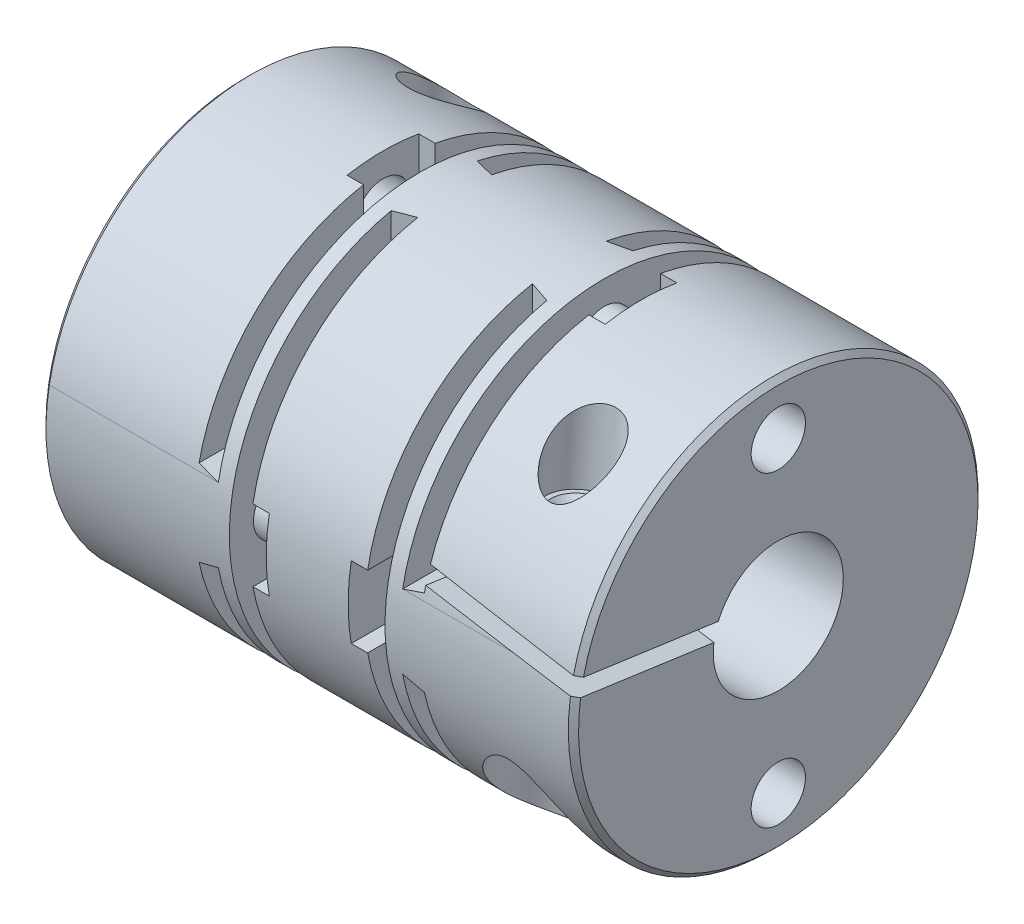
SolidWorks part; units mm, degrees
ref_plane "Front Plane" through (0, 0, 0) normal (0, 0, 1) x (1, 0, 0)
ref_plane "Top Plane" through (0, 0, 0) normal (0, 1, 0) x (1, 0, 0)
ref_plane "Right Plane" through (0, 0, 0) normal (1, 0, 0) x (0, 0, -1)
ref_plane "Plane1" through (0, 0, 0) normal (0, 0, 1) x (1, 0, 0)
sketch "Sketch1" plane through (0, 0, 0) normal (0, 0, 1) x (1, 0, 0)
  line L0 (0, 3.175) -> (7.5, 3.175)
  line L1 (7.5, 3.175) -> (7.5, 4.05)
  line L2 (7.5, 4.05) -> (18.5, 4.05)
  line L3 (18.5, 4.05) -> (18.5, 3.175)
  line L4 (18.5, 3.175) -> (26, 3.175)
  line L5 (26, 3.175) -> (26, 9.75)
  line L6 (26, 9.75) -> (25.75, 10)
  line L7 (25.75, 10) -> (0.25, 10)
  line L8 (0.25, 10) -> (0, 9.75)
  line L9 (0, 9.75) -> (0, 3.175)
  line L10 (26, 0) -> (0, 0) construction
revolve "Revolve1" add sketch "Sketch1" angle 360 about L10 reverse direction yes
ref_plane "Plane2" through (0, 0, 0) normal (0, -0.1392, 0.9903) x (1, 0, 0)
sketch "Sketch2" plane through (0, 0, 0) normal (0, -0.1392, 0.9903) x (1, 0, 0)
  line L0 (-1.3514, 1.4356) -> (-1.24, 0.6434)
  line L1 (-1.24, 0.6434) -> (8.5, 2.0122)
  line L2 (8.5, 2.0122) -> (8.5, 2.8201)
  line L3 (8.5, 2.8201) -> (-1.3514, 1.4356)
extrude "Cut-Extrude1" cut sketch "Sketch2" against normal blind 10
ref_plane "Plane3" through (0, 0, 0) normal (0, 0.1392, 0.9903) x (1, 0, 0)
sketch "Sketch3" plane through (0, 0, 0) normal (0, 0.1392, 0.9903) x (1, 0, 0)
  line L0 (17.5, 1.1492) -> (26, 0)
  line L1 (26, 0) -> (26.1072, 0.7928)
  line L2 (26.1072, 0.7928) -> (17.5, 1.9565)
  line L3 (17.5, 1.9565) -> (17.5, 1.1492)
extrude "Cut-Extrude2" cut sketch "Sketch3" along normal blind 10
ref_plane "Plane4" through (3.7, 0, 0) normal (1, 0, 0) x (0, 0, -1)
sketch "Sketch4" plane through (3.7, 0, 0) normal (1, 0, 0) x (0, 0, -1)
  line L0 (5.6037, 10.5285) -> (7.098, 10.6592)
  line L1 (7.098, 10.6592) -> (7.5338, 5.6782)
  line L2 (7.5338, 5.6782) -> (7.2847, 5.6564)
  line L3 (7.2847, 5.6564) -> (7.0634, 5.3926)
  line L4 (7.0634, 5.3926) -> (7.4567, 0.8968)
  line L5 (7.4567, 0.8968) -> (7.7205, 0.6755)
  line L6 (7.7205, 0.6755) -> (7.982, -2.3131)
  line L7 (7.982, -2.3131) -> (9.4016, -2.1889)
  line L8 (9.4016, -2.1889) -> (10.0116, -9.1623)
  line L9 (10.0116, -9.1623) -> (7.3468, -9.3954)
  line L10 (7.3468, -9.3954) -> (5.6037, 10.5285)
  line L11 (7.3468, -9.3954) -> (5.6037, 10.5285) construction
revolve "Cut-Revolve1" cut sketch "Sketch4" angle 360 about L11 reverse direction yes
ref_plane "Plane5" through (22.3, 0, 0) normal (1, 0, 0) x (0, 0, -1)
sketch "Sketch5" plane through (22.3, 0, 0) normal (1, 0, 0) x (0, 0, -1)
  line L0 (-5.6037, 10.5285) -> (-4.1094, 10.3977)
  line L1 (-4.1094, 10.3977) -> (-4.5452, 5.4168)
  line L2 (-4.5452, 5.4168) -> (-4.7942, 5.4385)
  line L3 (-4.7942, 5.4385) -> (-5.058, 5.2172)
  line L4 (-5.058, 5.2172) -> (-5.3816, 1.5183)
  line L5 (-5.3816, 1.5183) -> (-5.1603, 1.2545)
  line L6 (-5.1603, 1.2545) -> (-5.4915, -2.531)
  line L7 (-5.4915, -2.531) -> (-4.0719, -2.6552)
  line L8 (-4.0719, -2.6552) -> (-4.682, -9.6286)
  line L9 (-4.682, -9.6286) -> (-7.3468, -9.3954)
  line L10 (-7.3468, -9.3954) -> (-5.6037, 10.5285)
  line L11 (-7.3468, -9.3954) -> (-5.6037, 10.5285) construction
revolve "Cut-Revolve2" cut sketch "Sketch5" angle 360 about L11 reverse direction yes
ref_plane "Plane6" through (0, 0, 0) normal (0, 0, 1) x (1, 0, 0)
sketch "Sketch6" plane through (0, 0, 0) normal (0, 0, 1) x (1, 0, 0)
  line L0 (7.5, 10.5) -> (7.5, 2.1)
  line L1 (7.5, 2.1) -> (8.5, 1.8)
  line L2 (8.5, 1.8) -> (8.5, 10)
  line L3 (8.5, 10) -> (17.5, 10)
  line L4 (17.5, 10) -> (17.5, 1.8)
  line L5 (17.5, 1.8) -> (18.5, 2.1)
  line L6 (18.5, 2.1) -> (18.5, 10.5)
  line L7 (18.5, 10.5) -> (7.5, 10.5)
extrude "Cut-Extrude3" cut sketch "Sketch6" against normal blind 10 and the other way blind 10
ref_plane "Plane7" through (0, 0, 0) normal (0, 0, 1) x (1, 0, 0)
sketch "Sketch7" plane through (0, 0, 0) normal (0, 0, 1) x (1, 0, 0)
  line L0 (7.5, -10.5) -> (18.5, -10.5)
  line L1 (18.5, -10.5) -> (18.5, -2.1)
  line L2 (18.5, -2.1) -> (17.5, -1.8)
  line L3 (17.5, -1.8) -> (17.5, -10)
  line L4 (17.5, -10) -> (8.5, -10)
  line L5 (8.5, -10) -> (8.5, -1.8)
  line L6 (8.5, -1.8) -> (7.5, -2.1)
  line L7 (7.5, -2.1) -> (7.5, -10.5)
extrude "Cut-Extrude4" cut sketch "Sketch7" against normal blind 10 and the other way blind 10
ref_plane "Plane8" through (0, 0, 0) normal (0, 1, 0) x (-1, 0, 0)
sketch "Sketch8" plane through (0, 0, 0) normal (0, 1, 0) x (-1, 0, 0)
  line L0 (-9.2, -10.5) -> (-9.2, -2.1)
  line L1 (-9.2, -2.1) -> (-10.2, -1.8)
  line L2 (-10.2, -1.8) -> (-10.2, -10)
  line L3 (-10.2, -10) -> (-15.8, -10)
  line L4 (-15.8, -10) -> (-15.8, -1.8)
  line L5 (-15.8, -1.8) -> (-16.8, -2.1)
  line L6 (-16.8, -2.1) -> (-16.8, -10.5)
  line L7 (-16.8, -10.5) -> (-9.2, -10.5)
extrude "Cut-Extrude5" cut sketch "Sketch8" against normal blind 10 and the other way blind 10
ref_plane "Plane9" through (0, 0, 0) normal (0, 1, 0) x (-1, 0, 0)
sketch "Sketch9" plane through (0, 0, 0) normal (0, 1, 0) x (-1, 0, 0)
  line L0 (-9.2, 10.5) -> (-16.8, 10.5)
  line L1 (-16.8, 10.5) -> (-16.8, 2.1)
  line L2 (-16.8, 2.1) -> (-15.8, 1.8)
  line L3 (-15.8, 1.8) -> (-15.8, 10)
  line L4 (-15.8, 10) -> (-10.2, 10)
  line L5 (-10.2, 10) -> (-10.2, 1.8)
  line L6 (-10.2, 1.8) -> (-9.2, 2.1)
  line L7 (-9.2, 2.1) -> (-9.2, 10.5)
extrude "Cut-Extrude6" cut sketch "Sketch9" against normal blind 10 and the other way blind 10
ref_plane "Plane10" through (15.8, 0, 0) normal (1, 0, 0) x (0, 0, -1)
sketch "Sketch10" plane through (15.8, 0, 0) normal (1, 0, 0) x (0, 0, -1)
  line L0 (-10, -1.75) -> (-7.5, -1.75)
  line L1 (-7.5, 1.75) -> (-10, 1.75)
  line L2 (-10, 1.75) -> (-10, -1.75)
  arc A0 (-7.5, -1.75) -> (-7.5, 1.75) centre (-7.5, 0) ccw
extrude "Cut-Extrude7" cut sketch "Sketch10" against normal blind 0.8
ref_plane "Plane11" through (15.8, 0, 0) normal (1, 0, 0) x (0, 0, -1)
sketch "Sketch11" plane through (15.8, 0, 0) normal (1, 0, 0) x (0, 0, -1)
  line L0 (7.5, -1.75) -> (10, -1.75)
  line L1 (10, -1.75) -> (10, 1.75)
  line L2 (10, 1.75) -> (7.5, 1.75)
  arc A0 (7.5, 1.75) -> (7.5, -1.75) centre (7.5, 0) ccw
extrude "Cut-Extrude8" cut sketch "Sketch11" against normal blind 0.8
ref_plane "Plane12" through (10.2, 0, 0) normal (1, 0, 0) x (0, 0, -1)
sketch "Sketch12" plane through (10.2, 0, 0) normal (1, 0, 0) x (0, 0, -1)
  line L0 (-10, -1.75) -> (-7.5, -1.75)
  line L1 (-7.5, 1.75) -> (-10, 1.75)
  line L2 (-10, 1.75) -> (-10, -1.75)
  arc A0 (-7.5, -1.75) -> (-7.5, 1.75) centre (-7.5, 0) ccw
extrude "Cut-Extrude9" cut sketch "Sketch12" along normal blind 0.8
ref_plane "Plane13" through (10.2, 0, 0) normal (1, 0, 0) x (0, 0, -1)
sketch "Sketch13" plane through (10.2, 0, 0) normal (1, 0, 0) x (0, 0, -1)
  line L0 (7.5, -1.75) -> (10, -1.75)
  line L1 (10, -1.75) -> (10, 1.75)
  line L2 (10, 1.75) -> (7.5, 1.75)
  arc A0 (7.5, 1.75) -> (7.5, -1.75) centre (7.5, 0) ccw
extrude "Cut-Extrude10" cut sketch "Sketch13" along normal blind 0.8
ref_plane "Plane14" through (7.5, 0, 0) normal (1, 0, 0) x (0, 0, -1)
sketch "Sketch14" plane through (7.5, 0, 0) normal (1, 0, 0) x (0, 0, -1)
  line L0 (1.75, 7.5) -> (1.75, 10)
  line L1 (1.75, 10) -> (-1.75, 10)
  line L2 (-1.75, 10) -> (-1.75, 7.5)
  arc A0 (-1.75, 7.5) -> (1.75, 7.5) centre (0, 7.5) ccw
extrude "Cut-Extrude11" cut sketch "Sketch14" against normal blind 0.8
ref_plane "Plane15" through (7.5, 0, 0) normal (1, 0, 0) x (0, 0, -1)
sketch "Sketch15" plane through (7.5, 0, 0) normal (1, 0, 0) x (0, 0, -1)
  line L0 (-1.75, -7.5) -> (-1.75, -10)
  line L1 (-1.75, -10) -> (1.75, -10)
  line L2 (1.75, -10) -> (1.75, -7.5)
  arc A0 (1.75, -7.5) -> (-1.75, -7.5) centre (0, -7.5) ccw
extrude "Cut-Extrude12" cut sketch "Sketch15" against normal blind 0.8
ref_plane "Plane16" through (18.5, 0, 0) normal (1, 0, 0) x (0, 0, -1)
sketch "Sketch16" plane through (18.5, 0, 0) normal (1, 0, 0) x (0, 0, -1)
  line L0 (1.75, 7.5) -> (1.75, 10)
  line L1 (1.75, 10) -> (-1.75, 10)
  line L2 (-1.75, 10) -> (-1.75, 7.5)
  arc A0 (-1.75, 7.5) -> (1.75, 7.5) centre (0, 7.5) ccw
extrude "Cut-Extrude13" cut sketch "Sketch16" along normal blind 0.8
ref_plane "Plane17" through (18.5, 0, 0) normal (1, 0, 0) x (0, 0, -1)
sketch "Sketch17" plane through (18.5, 0, 0) normal (1, 0, 0) x (0, 0, -1)
  line L0 (-1.75, -7.5) -> (-1.75, -10)
  line L1 (-1.75, -10) -> (1.75, -10)
  line L2 (1.75, -10) -> (1.75, -7.5)
  arc A0 (1.75, -7.5) -> (-1.75, -7.5) centre (0, -7.5) ccw
extrude "Cut-Extrude14" cut sketch "Sketch17" along normal blind 0.8
ref_plane "Plane18" through (9.2, 0, 0) normal (1, 0, 0) x (0, 0, -1)
sketch "Sketch18" plane through (9.2, 0, 0) normal (1, 0, 0) x (0, 0, -1)
  circle A0 centre (-7.5, 0) radius 1.325
extrude "Boss-Extrude1" add sketch "Sketch18" along normal blind 0.8
ref_plane "Plane19" through (9.2, 0, 0) normal (1, 0, 0) x (0, 0, -1)
sketch "Sketch19" plane through (9.2, 0, 0) normal (1, 0, 0) x (0, 0, -1)
  circle A0 centre (7.5, 0) radius 1.325
extrude "Boss-Extrude2" add sketch "Sketch19" along normal blind 0.8
ref_plane "Plane20" through (8.5, 0, 0) normal (1, 0, 0) x (0, 0, -1)
sketch "Sketch20" plane through (8.5, 0, 0) normal (1, 0, 0) x (0, 0, -1)
  circle A0 centre (0, 7.5) radius 1.325
extrude "Boss-Extrude3" add sketch "Sketch20" against normal blind 0.8
ref_plane "Plane21" through (8.5, 0, 0) normal (1, 0, 0) x (0, 0, -1)
sketch "Sketch21" plane through (8.5, 0, 0) normal (1, 0, 0) x (0, 0, -1)
  circle A0 centre (0, -7.5) radius 1.325
extrude "Boss-Extrude4" add sketch "Sketch21" against normal blind 0.8
ref_plane "Plane22" through (16.8, 0, 0) normal (1, 0, 0) x (0, 0, -1)
sketch "Sketch22" plane through (16.8, 0, 0) normal (1, 0, 0) x (0, 0, -1)
  circle A0 centre (-7.5, 0) radius 1.325
extrude "Boss-Extrude5" add sketch "Sketch22" against normal blind 0.8
ref_plane "Plane23" through (16.8, 0, 0) normal (1, 0, 0) x (0, 0, -1)
sketch "Sketch23" plane through (16.8, 0, 0) normal (1, 0, 0) x (0, 0, -1)
  circle A0 centre (7.5, 0) radius 1.325
extrude "Boss-Extrude6" add sketch "Sketch23" against normal blind 0.8
ref_plane "Plane24" through (17.5, 0, 0) normal (1, 0, 0) x (0, 0, -1)
sketch "Sketch24" plane through (17.5, 0, 0) normal (1, 0, 0) x (0, 0, -1)
  circle A0 centre (0, 7.5) radius 1.325
extrude "Boss-Extrude7" add sketch "Sketch24" along normal blind 0.8
ref_plane "Plane25" through (17.5, 0, 0) normal (1, 0, 0) x (0, 0, -1)
sketch "Sketch25" plane through (17.5, 0, 0) normal (1, 0, 0) x (0, 0, -1)
  circle A0 centre (0, -7.5) radius 1.325
extrude "Boss-Extrude8" add sketch "Sketch25" along normal blind 0.8
ref_plane "Plane26" through (0, 0, 0) normal (1, 0, 0) x (0, 0, -1)
sketch "Sketch26" plane through (0, 0, 0) normal (1, 0, 0) x (0, 0, -1)
  circle A0 centre (0, 7.5) radius 1.325
extrude "Cut-Extrude15" cut sketch "Sketch26" along normal blind 7.5
ref_plane "Plane27" through (0, 0, 0) normal (1, 0, 0) x (0, 0, -1)
sketch "Sketch27" plane through (0, 0, 0) normal (1, 0, 0) x (0, 0, -1)
  circle A0 centre (0, -7.5) radius 1.325
extrude "Cut-Extrude16" cut sketch "Sketch27" along normal blind 7.5
ref_plane "Plane28" through (26, 0, 0) normal (1, 0, 0) x (0, 0, -1)
sketch "Sketch28" plane through (26, 0, 0) normal (1, 0, 0) x (0, 0, -1)
  circle A0 centre (0, 7.5) radius 1.325
extrude "Cut-Extrude17" cut sketch "Sketch28" against normal blind 7.5
ref_plane "Plane29" through (26, 0, 0) normal (1, 0, 0) x (0, 0, -1)
sketch "Sketch29" plane through (26, 0, 0) normal (1, 0, 0) x (0, 0, -1)
  circle A0 centre (0, -7.5) radius 1.325
extrude "Cut-Extrude18" cut sketch "Sketch29" against normal blind 7.5
